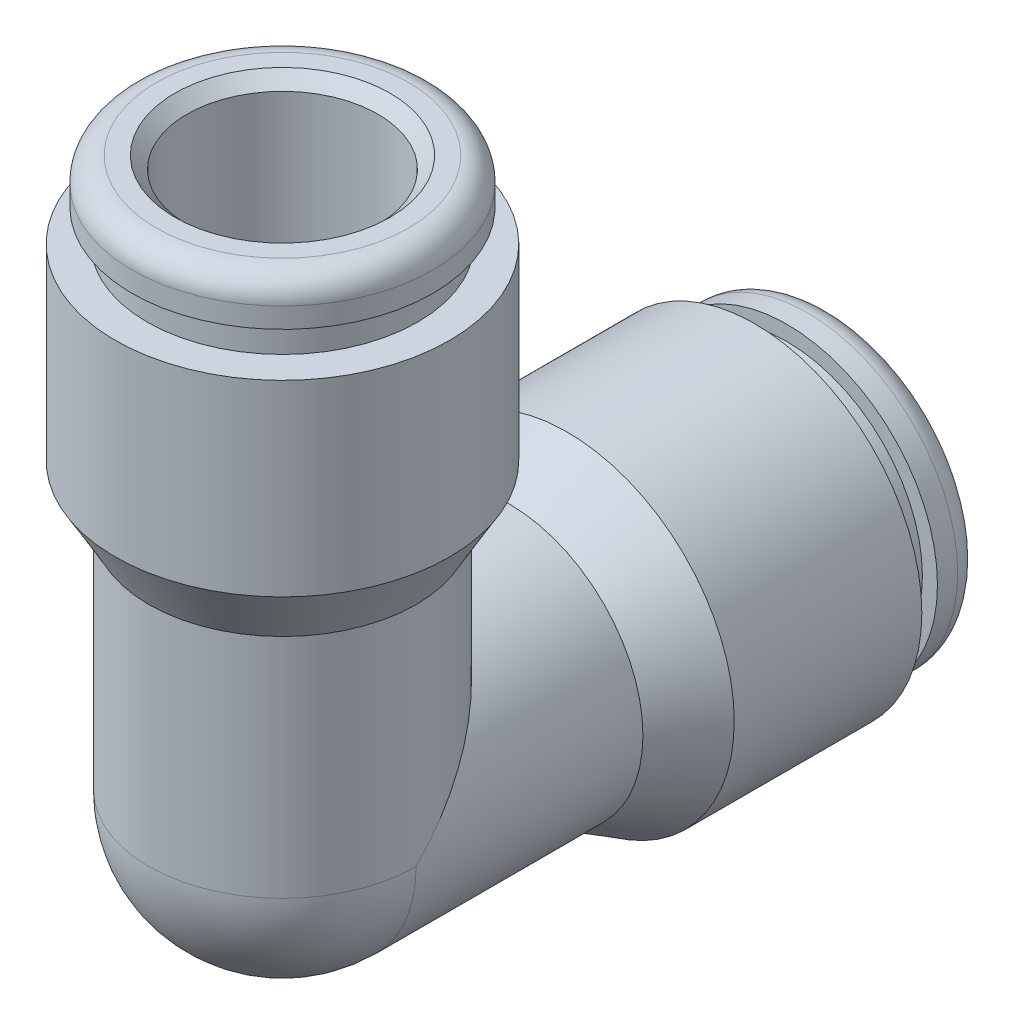
SolidWorks part; units mm, degrees
ref_plane "Front Plane" through (0, 0, 0) normal (0, 0, 1) x (1, 0, 0)
ref_plane "Top Plane" through (0, 0, 0) normal (0, 1, 0) x (1, 0, 0)
ref_plane "Right Plane" through (0, 0, 0) normal (1, 0, 0) x (0, 0, -1)
sketch "Sketch1" plane through (0, 0, 0) normal (1, 0, 0) x (0, 0, -1)
  line L0 (15.853, 4.725) -> (16.488, 4.725)
  line L1 (8.9437, 5.25) -> (14.837, 5.25)
  line L2 (0, 4.2) -> (0, 2.238)
  line L3 (6, 3) -> (16.869, 3)
  line L4 (17.25, 3.963) -> (17.25, 3.381)
  line L5 (0, 0) -> (0, 17.25) construction
  line L6 (14.837, 5.25) -> (14.837, 4.2525)
  line L7 (14.837, 4.2525) -> (15.853, 4.2525)
  line L8 (15.853, 4.725) -> (15.853, 4.2525)
  line L9 (-5.25, 17.25) -> (5.25, 17.25) construction
  line L10 (0, 0) -> (17.25, 0) construction
  line L11 (6, 3) -> (6, 2.238)
  line L12 (16.869, 3) -> (17.25, 3.381)
  line L13 (0, 0) -> (0, 2.238) construction
  line L14 (0, 4.2) -> (7.125, 4.2)
  line L15 (7.125, 4.2) -> (8.9437, 5.25)
  line L16 (6, 2.238) -> (0, 2.238)
  arc A0 (16.488, 4.725) -> (17.25, 3.963) centre (16.488, 3.963) cw
  point P1 (17.25, 3)
  point P20 (17.25, 4.725)
  dimension "D4" = 0.762
  dimension "tube od" = 6
  dimension "D1" = 1.397
  dimension "D2" = 1.016
  dimension "D3" = 8.505
  dimension "D6" = 9.45
  dimension "D9" = 30
  dimension "D10" = 8.4
  dimension "D5" = 10.125
  dimension "D8" = 10.5
  dimension "D11" = 0.762
revolve "Revolve1" add sketch "Sketch1" angle 360 about L10
ref_axis "Axis1" through (-15.8019, 0, 0) along (1, 0, 0)
pattern_circular "CirPattern1" count 2 over 90 about axis through (-15.8019, 0, 0) along (1, 0, 0) of bodies 118 123
sketch "Sketch2" plane through (0, 0, 0) normal (0, 0, 1) x (1, 0, 0)
  line L0 (-4.2, 0) -> (-2.238, 0)
  line L1 (-4.2, 0) -> (4.2, 0) construction
  line L2 (2.238, 0) -> (4.2, 0)
  arc A0 (-4.2, 0) -> (4.2, 0) centre (0, 0) ccw
  arc A2 (-2.238, 0) -> (2.238, 0) centre (0, 0) ccw
  circle A4 centre (0, 0) radius 2.238 construction
  circle A5 centre (0, 0) radius 4.2 construction
revolve "Revolve2" add sketch "Sketch2" angle 90 about L1 reverse direction yes
combine bodies "Combine1" operation type add bodies to combine 122 124
sketch "Sketch3" plane through (0, 0, 0) normal (1, 0, 0) x (0, 0, -1)
  line L0 (17.25, 3.381) -> (16.869, 3)
  line L1 (16.869, 3) -> (6, 3)
  line L2 (6, 3) -> (6, 2.238)
  line L3 (6, 2.238) -> (0, 2.238)
  line L4 (0, 2.238) -> (0, 0)
  line L5 (0, 0) -> (17.25, 0)
  line L6 (17.25, 0) -> (17.25, 3.381)
revolve "Cut-Revolve1" cut sketch "Sketch3" angle 360 about L5
pattern_circular "CirPattern2" count 2 over 90 about axis through (-15.8019, 0, 0) along (1, 0, 0) of "Cut-Revolve1"
equation "\"D6@Sketch1\" = \"G@Sketch1\"*.9"
equation "\"D3@Sketch1\" = \"D6@Sketch1\"*.9"
equation "\"D10@Sketch1\" = \"G@Sketch1\"*.8"
equation "\"D5@Sketch1\" = \"L@Sketch1\"*.45"
equation "\"D8@Sketch1\" = \"G@Sketch1\""
